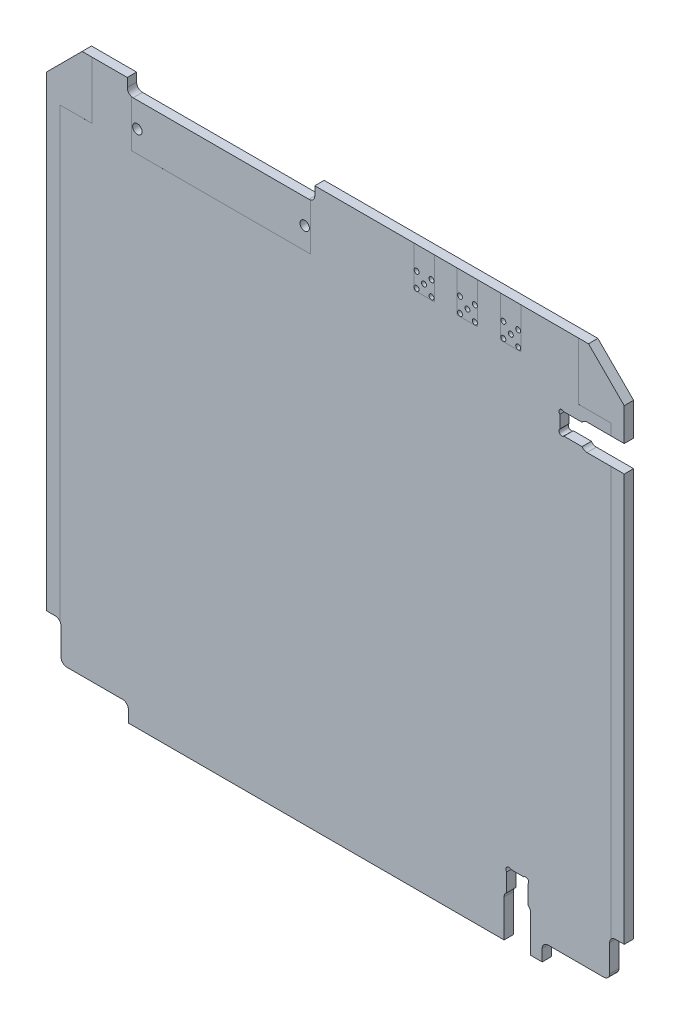
SolidWorks part; units mm, degrees
ref_plane "Front Plane" through (0, 0, 0) normal (0, 0, 1) x (1, 0, 0)
ref_plane "Top Plane" through (0, 0, 0) normal (0, 1, 0) x (1, 0, 0)
ref_plane "Right Plane" through (0, 0, 0) normal (1, 0, 0) x (0, 0, -1)
ref_plane "Plane4" through (0, 0, -0.0125) normal (0, 0, -1) x (-1, 0, 0)
sketch "Sketch1" plane through (0, 0, -0.0125) normal (0, 0, -1) x (-1, 0, 0)
  line L0 (35.3, -50) -> (35.3, -48)
  line L1 (36.3, -47) -> (45.8, -47)
  line L2 (46.8, -46) -> (46.8, -41.4)
  line L3 (47.8, -40.4) -> (49.3, -40.4)
  line L4 (49.3, -40.4) -> (49.3, 39.2)
  line L5 (49.3, 39.2) -> (43.2, 45.3)
  line L6 (43.2, 45.3) -> (35.5, 45.3)
  line L7 (35.5, 45.3) -> (35.5, 43.8)
  line L8 (34.5, 42.8) -> (4.5, 42.8)
  line L9 (3.5, 43.8) -> (3.5, 45.3)
  line L10 (3.5, 45.3) -> (-43.2, 45.3)
  line L11 (-43.2, 45.3) -> (-49.3, 39.2)
  line L12 (-49.3, 39.2) -> (-49.3, -40.4)
  line L13 (-49.3, -40.4) -> (-47.8, -40.4)
  line L14 (-46.8, -41.4) -> (-46.8, -46)
  line L15 (-45.8, -47) -> (-36.3, -47)
  line L16 (-35.3, -48) -> (-35.3, -50)
  line L17 (-35.3, -50) -> (35.3, -50)
  line L18 (0, -50) -> (0, 45.3) construction
  line L19 (19.5, 42.8) -> (19.5, 25.5258) construction
  line L20 (-13.87, 41.37) -> (-16.41, 38.83) construction
  line L21 (-21.27, 41.37) -> (-23.81, 38.83) construction
  line L22 (-28.67, 41.37) -> (-31.21, 38.83) construction
  arc A0 (35.3, -48) -> (36.3, -47) centre (36.3, -48) cw
  arc A1 (45.8, -47) -> (46.8, -46) centre (45.8, -46) ccw
  arc A2 (46.8, -41.4) -> (47.8, -40.4) centre (47.8, -41.4) cw
  arc A3 (35.5, 43.8) -> (34.5, 42.8) centre (34.5, 43.8) cw
  arc A4 (4.5, 42.8) -> (3.5, 43.8) centre (4.5, 43.8) cw
  arc A5 (-47.8, -40.4) -> (-46.8, -41.4) centre (-47.8, -41.4) cw
  arc A6 (-46.8, -46) -> (-45.8, -47) centre (-45.8, -46) ccw
  arc A7 (-36.3, -47) -> (-35.3, -48) centre (-36.3, -48) cw
  circle A8 centre (-21.27, 41.37) radius 0.425
  circle A9 centre (-23.81, 41.37) radius 0.425
  circle A10 centre (-22.54, 40.1) radius 0.425
  circle A11 centre (-13.87, 41.37) radius 0.425
  circle A12 centre (-23.81, 38.83) radius 0.425
  circle A13 centre (-16.41, 41.37) radius 0.425
  circle A14 centre (-15.14, 40.1) radius 0.425
  circle A15 centre (-21.27, 38.83) radius 0.425
  circle A16 centre (-28.67, 41.37) radius 0.425
  circle A17 centre (-31.21, 41.37) radius 0.425
  circle A18 centre (-16.41, 38.83) radius 0.425
  circle A19 centre (-29.94, 40.1) radius 0.425
  circle A20 centre (-31.21, 38.83) radius 0.425
  circle A21 centre (-28.67, 38.83) radius 0.425
  circle A22 centre (33.775, 38.54) radius 0.8
  circle A23 centre (5.225, 38.54) radius 0.8
  circle A24 centre (-13.87, 38.83) radius 0.425
  point P35 (-15.14, 40.1)
  dimension "D7" = 2.5
  dimension "D8" = 1.6
  dimension "D9" = 14.275
  dimension "D10" = 4.26
  dimension "D11" = 1
  dimension "D12" = 1
  dimension "D13" = 1
  dimension "D14" = 1
  dimension "D15" = 1
  dimension "D16" = 1
  dimension "D17" = 1
  dimension "D18" = 1
  dimension "D26" = 0.85
  dimension "D1" = 98.6
  dimension "D2" = 95.3
  dimension "D3" = 14
  dimension "D4" = 9.6
  dimension "D5" = 2.5
  dimension "D6" = 3
  dimension "D19" = 14
  dimension "D20" = 2.5
  dimension "D21" = 6.1
  dimension "D22" = 6.1
  dimension "D23" = 32
  dimension "D24" = 2.54
  dimension "D25" = 2.54
  dimension "D28" = 7.4
  dimension "D29" = 3.93
  dimension "D30" = 35.43
  dimension "D31" = 45
  dimension "D32" = 45
  dimension "D33" = 29.8
  dimension "D34" = 50
  dimension "D27" = 3
extrude "Boss-Extrude1" add sketch "Sketch1" against normal blind 1.6
sketch "thermalContacts_lower" plane through (0, 0, -0.0125) normal (0, 0, -1) x (-1, 0, 0)
  line L0 (47, 35.5) -> (47, -41.5) construction
  line L1 (41.5, 35.5) -> (41.5, 41.5) construction
  line L2 (41.5, 35.5) -> (47, 35.5) construction
  line L3 (47, 35.5) -> (47, -41.5)
  line L4 (41.5, 35.5) -> (41.5, 41.5)
  line L5 (41.5, 35.5) -> (47, 35.5)
  line L6 (-47, 35.5) -> (-47, -41.5) construction
  line L7 (-41.5, 35.5) -> (-47, 35.5) construction
  line L8 (-41.5, 35.5) -> (-41.5, 41.5) construction
  line L9 (-47, 35.5) -> (-47, -41.5)
  line L10 (-41.5, 35.5) -> (-47, 35.5)
  line L11 (-41.5, 35.5) -> (-41.5, 41.5)
  line L12 (-41.5, 41.5) -> (-41.5, 47) construction
  line L13 (-41.5, 41.5) -> (-49.5, 41.5) construction
  line L14 (-41.5, 41.5) -> (-41.5, 47)
  line L15 (-41.5, 41.5) -> (-49.5, 41.5) construction
  line L16 (41.5, 41.5) -> (41.5, 47) construction
  line L17 (41.5, 41.5) -> (49.5, 41.5) construction
  line L18 (41.5, 41.5) -> (41.5, 47)
  line L19 (41.5, 41.5) -> (49.5, 41.5) construction
  line L20 (47, -41.5) -> (59.8273, -41.5)
  line L21 (59.8273, -41.5) -> (59.8273, 47)
  line L22 (-56.1922, 47) -> (-41.5, 47)
  line L23 (41.5, 47) -> (59.8273, 47)
  line L24 (-56.1922, 47) -> (-56.1922, -41.5)
  line L25 (-47, -41.5) -> (-56.1922, -41.5)
sketch "thermalContacts_upper" plane through (0, 0, 1.5875) normal (0, 0, 1) x (1, 0, 0)
  line L3 (-47, 35.5) -> (-47, -41.5)
  line L4 (-41.5, 35.5) -> (-41.5, 41.5)
  line L5 (-41.5, 35.5) -> (-47, 35.5)
  line L9 (47, 35.5) -> (47, -41.5)
  line L10 (41.5, 35.5) -> (47, 35.5)
  line L11 (41.5, 35.5) -> (41.5, 41.5)
  line L14 (41.5, 41.5) -> (41.5, 47)
  line L15 (41.5, 41.5) -> (49.5, 41.5) construction
  line L18 (-41.5, 41.5) -> (-41.5, 47)
  line L19 (-41.5, 41.5) -> (-49.5, 41.5) construction
  line L20 (47, -41.5) -> (59.8273, -41.5)
  line L21 (59.8273, -41.5) -> (59.8273, 47)
  line L22 (59.8273, 47) -> (41.5, 47)
  line L23 (-41.5, 47) -> (-56.1922, 47)
  line L24 (-56.1922, 47) -> (-56.1922, -41.5)
  line L25 (-56.1922, -41.5) -> (-47, -41.5)
extrude "Cut-Extrude1" cut sketch "thermalContacts_lower" against normal blind 0.0001
extrude "Cut-Extrude2" cut sketch "thermalContacts_upper" against normal blind 0.0001
sketch "partFootprints" plane through (0, 0, 1.5875) normal (0, 0, 1) x (1, 0, 0)
  line L0 (-34.74, 34.84) -> (-34.74, 42.8292)
  line L1 (-4.26, 34.84) -> (-34.74, 34.84)
  line L2 (-41.5, 45.3) -> (-35.5, 45.3) construction
  line L3 (-36.1132, 45.3) -> (-39.5054, 45.3) construction
  line L4 (-4.26, 34.84) -> (-4.26, 42.8292)
  line L5 (-49.3, -40.4) -> (-49.3, 39.2) construction
  line L6 (13.39, 45.3) -> (13.39, 38.35)
  line L7 (13.39, 38.35) -> (16.89, 38.35)
  line L8 (16.89, 38.35) -> (16.89, 45.3)
  line L9 (16.89, 45.3) -> (13.39, 45.3)
  line L10 (20.79, 45.3) -> (20.79, 38.35)
  line L11 (20.79, 38.35) -> (24.29, 38.35)
  line L12 (24.29, 38.35) -> (24.29, 45.3)
  line L13 (24.29, 45.3) -> (20.79, 45.3)
  line L14 (28.19, 45.3) -> (28.19, 38.35)
  line L15 (28.19, 38.35) -> (31.69, 38.35)
  line L16 (31.69, 38.35) -> (31.69, 45.3)
  line L17 (31.69, 45.3) -> (28.19, 45.3)
  line L19 (14.12, 38.35) -> (16.16, 38.35) construction
  line L20 (-34.74, 42.8292) -> (-4.26, 42.8292)
  line L21 (-3.5, 45.3) -> (41.5, 45.3) construction
  line L22 (14.12, 38.35) -> (16.16, 38.35) construction
  line L23 (13.39, 41.85) -> (13.39, 38.35) construction
  line L24 (16.89, 41.85) -> (16.89, 38.35) construction
  line L25 (13.39, 41.85) -> (13.39, 38.35) construction
  line L26 (16.89, 41.85) -> (16.89, 38.35) construction
  arc A0 (-35.5, 43.8) -> (-34.5, 42.8) centre (-34.5, 43.8) ccw construction
  arc A1 (-4.5, 42.8) -> (-3.5, 43.8) centre (-4.5, 43.8) ccw construction
  dimension "D1" = 10.46
  dimension "D2" = 14.56
  dimension "D3" = 30.48
  dimension "D7" = 7.4
  dimension "D6" = 3
extrude "Cut-Extrude3" cut sketch "partFootprints" against normal blind 0.0001
sketch "Sketch2" plane through (0, 0, 1.5875) normal (0, 0, 1) x (1, 0, 0)
  line L0 (35.1, -50) -> (35.1, -37.1982) construction
  line L1 (35.3, -50) -> (-35.3, -50) construction
  line L2 (27, -50) -> (27, -36.5559) construction
  line L3 (35.3, -48) -> (35.3, -50) construction
  line L4 (29.25, -42.8) -> (29.25, -39.7071)
  line L5 (27, -39) -> (35.1, -39) construction
  line L6 (29.9571, -39) -> (32.1429, -39)
  line L7 (32.85, -39.7071) -> (32.85, -42.8)
  line L8 (28.8, -50) -> (33.3, -50)
  line L9 (29.9571, -39) -> (32.1429, -39) construction
  line L10 (28.8, -50) -> (28.8, -42.8)
  line L11 (28.8, -42.8) -> (29.25, -42.8)
  line L12 (31.05, -39) -> (31.05, -50) construction
  line L13 (33.3, -42.8) -> (32.85, -42.8)
  line L14 (33.3, -50) -> (33.3, -42.8)
  line L15 (48.0683, 27.2) -> (36.7758, 27.2) construction
  line L16 (48.0683, 35.5) -> (35.6387, 35.5) construction
  line L17 (42.1, 29.55) -> (39.0071, 29.55)
  line L18 (38.3, 35.5) -> (38.3, 27.2) construction
  line L19 (38.3, 30.2571) -> (38.3, 32.4429)
  line L20 (39.0071, 33.15) -> (42.1, 33.15)
  line L21 (49.3, 29.1) -> (49.3, 33.6)
  line L22 (38.3, 30.2571) -> (38.3, 32.4429) construction
  line L23 (49.3, 29.1) -> (42.1, 29.1)
  line L24 (42.1, 29.1) -> (42.1, 29.55)
  line L25 (38.3, 31.35) -> (49.3, 31.35) construction
  line L26 (42.1, 33.6) -> (42.1, 33.15)
  line L27 (49.3, 33.6) -> (42.1, 33.6)
  line L28 (49.3, -40.4) -> (49.3, 39.2) construction
  line L30 (31.69, 45.3) -> (41.5, 45.3) construction
  arc A0 (29.25, -39.7071) -> (29.9571, -39) centre (29.6036, -39.3536) cw
  arc A1 (32.1429, -39) -> (32.85, -39.7071) centre (32.4964, -39.3536) cw
  arc A2 (39.0071, 29.55) -> (38.3, 30.2571) centre (38.6536, 29.9036) cw
  arc A3 (38.3, 32.4429) -> (39.0071, 33.15) centre (38.6536, 32.7964) cw
  point P8 (35.3, -49)
  point P13 (0, 0)
  point P20 (23.5317, -22.8835)
  point P21 (31.893, -11.6437)
  point P31 (27, -36.5559)
  point P39 (38.3, 31.35)
  point P46 (38.3, 31.35)
  point P47 (38.3, 29.55)
  point P48 (38.3, 33.15)
  point P55 (35.1, -37.1982)
  point P56 (35.1, -38.2473)
  point P57 (31.05, -39)
  point P58 (32.85, -39.9289)
  point P59 (32.85, -39)
  point P60 (29.25, -39)
  point P61 (36.9851, -35.5)
  point P62 (48.0683, -27.2)
  point P63 (35.6387, -27.2)
  point P64 (48.0683, -35.5)
  point P65 (34.0102, -35.5)
  point P66 (36.7758, -35.5)
  point P67 (41.8535, -10.244)
  dimension "D5" = 0.5
  dimension "D8" = 0.5
  dimension "D1" = 0.2
  dimension "D2" = 8.3
  dimension "D3" = 3.6
  dimension "D4" = 11
  dimension "D6" = 3.8
  dimension "D7" = 4.5
  dimension "D9" = 3.6
  dimension "D10" = 11
  dimension "D11" = 3.8
  dimension "D12" = 4.5
  dimension "D13" = 9.8
  dimension "D14" = 8.3
extrude "Cut-Extrude4" cut sketch "Sketch2" against normal through all
fillet "Fillet1" radius 1 4 edges at (33.3, -42.8, 0.7875) (28.8, -42.8, 0.7875) (42.1, 33.6, 0.7875) (42.1, 29.1, 0.7875)
